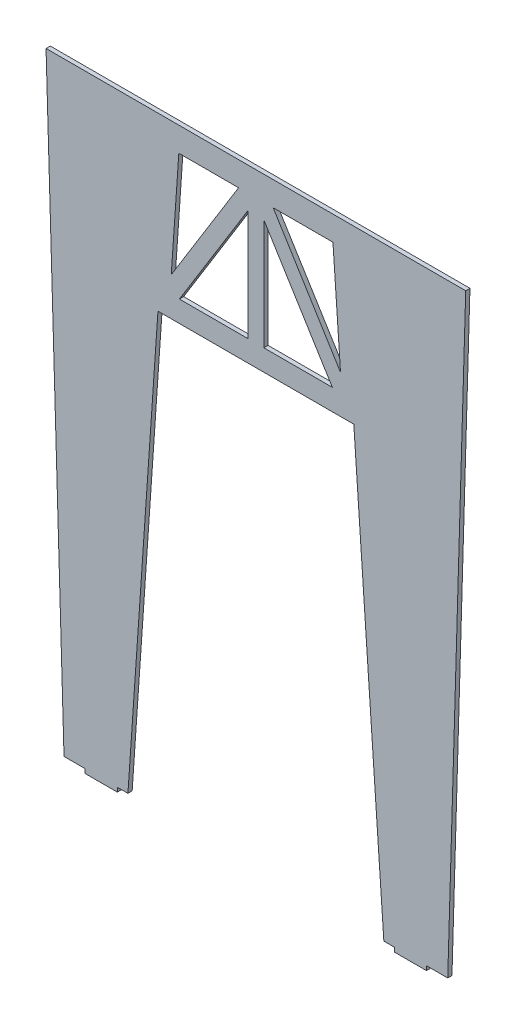
SolidWorks part; units mm, degrees
material "A-Glass Fiber"
ref_plane "Front Plane" through (0, 0, 0) normal (0, 0, 1) x (1, 0, 0)
ref_plane "Top Plane" through (0, 0, 0) normal (0, 1, 0) x (1, 0, 0)
ref_plane "Right Plane" through (0, 0, 0) normal (1, 0, 0) x (0, 0, -1)
sketch "Sketch1" plane through (0, 0, 0) normal (0, 0, 1) x (1, 0, 0)
  line L0 (-288.2759, 0) -> (288.2759, 0) construction
  line L1 (-215.8925, 1465.1633) -> (215.8925, 1465.1633)
  line L2 (0, 0) -> (0, 1733.4513) construction
  line L3 (19.05, 1104.9) -> (205.6376, 1104.9)
  line L4 (202.8026, 1145.716) -> (41.4459, 1406.7433)
  line L5 (205.6376, 1104.9) -> (19.05, 1406.7433) construction
  line L6 (205.6376, 1104.9) -> (184.6725, 1406.7433)
  line L7 (183.2417, 1104.9) -> (15.2162, 1376.7154)
  line L8 (19.05, 1406.7433) -> (19.05, 1104.9)
  line L9 (184.6725, 1406.7433) -> (19.05, 1406.7433)
  line L10 (306.6278, 17.4764) -> (234.6272, 1054.1)
  line L12 (459.7218, 17.4764) -> (502.7833, 1465.1633)
  line L13 (459.7218, 7.3164) -> (520.3601, 2060.2279) construction
  line L15 (266.6925, 1465.1633) -> (368.5375, 1465.1633)
  line L16 (-237.2124, 1016.8799) -> (-230.6925, 1110.7494) construction
  line L18 (237.2124, 1016.8799) -> (230.6925, 1110.7494) construction
  line L19 (-408.9218, 7.3164) -> (-332.1008, 7.3164)
  line L20 (-502.7833, 1465.1633) -> (-215.8925, 1465.1633)
  line L22 (408.9218, 7.3164) -> (332.7218, 7.3164)
  line L24 (-408.9218, 17.4764) -> (-408.9218, 7.3164) construction
  line L30 (-408.9218, 17.4764) -> (-408.9218, 7.3164)
  line L31 (502.7833, 1465.1633) -> (368.5375, 1465.1633)
  line L32 (-332.1008, 17.4764) -> (-332.1008, 7.3164) construction
  line L33 (-332.1008, 17.4764) -> (-332.1008, 7.3164)
  line L34 (408.9218, 17.4764) -> (408.9218, 7.3164) construction
  line L35 (408.9218, 17.4764) -> (408.9218, 7.3164)
  line L40 (332.7218, 17.4764) -> (332.7218, 7.3164) construction
  line L43 (332.7218, 17.4764) -> (332.7218, 7.3164)
  line L44 (459.7218, 17.4764) -> (408.9218, 17.4764) construction
  line L45 (459.7218, 17.4764) -> (408.9218, 17.4764)
  line L49 (-408.9218, 17.4764) -> (-459.7218, 17.4764)
  line L52 (-332.1008, 17.4764) -> (-306.6278, 17.4764)
  line L53 (332.7218, 17.4764) -> (306.6278, 17.4764)
  line L55 (-459.7218, 17.4764) -> (-502.7833, 1465.1633)
  line L56 (-459.7218, 7.3164) -> (-520.3601, 2060.2279) construction
  line L81 (215.8925, 1465.1633) -> (266.6925, 1465.1633)
  line L90 (234.6272, 1054.1) -> (-234.6272, 1054.1)
  line L100 (-234.6272, 1054.1) -> (-306.6278, 17.4764)
  line L124 (-184.6725, 1406.7433) -> (-19.05, 1406.7433)
  line L125 (-19.05, 1406.7433) -> (-19.05, 1104.9)
  line L126 (-183.2417, 1104.9) -> (-15.2162, 1376.7154)
  line L127 (-205.6376, 1104.9) -> (-19.05, 1406.7433) construction
  line L128 (-202.8026, 1145.716) -> (-41.4459, 1406.7433)
  line L129 (-205.6376, 1104.9) -> (-184.6725, 1406.7433)
  line L130 (-19.05, 1104.9) -> (-205.6376, 1104.9)
  point P0 (0, 0)
  point P1 (-316.1111, 17.4764)
  point P3 (0, 0)
  point P18 (450.2385, 17.4764)
  point P20 (307.2622, 17.4764)
  point P23 (0, 0)
  point P24 (-254.2769, 1054.1)
  point P36 (-244.1104, 1054.1)
  point P40 (-316.1111, 17.4764)
  point P41 (-326.2288, 18.1791)
  point P42 (0, 0)
  point P43 (225.1439, 1054.1)
  point P45 (299.3354, 17.4764)
  point P46 (0, 0)
  point P48 (0, 0)
  point P106 (0, 0)
  point P118 (0, 1054.1)
  dimension "D6" = 25.4
  dimension "D7" = 50.8
  dimension "D8" = 58.42
  dimension "D9" = 19.05
  dimension "D19" = 288.2759
  dimension "D22" = 19.05
  dimension "D23" = 19.05
  dimension "D24" = 1054.1
  dimension "D49" = 50.8
extrude "Boss-Extrude1" add sketch "Sketch1" along normal blind 10.16 contours L20 | L100 L90 L125 L130 L129 L124 | L100 | L130 L126 L125 L124 L128 L129 | L81 | L4 L9 L8 L7 L3 L6 | L15 region at (0, 1447.4532, 0) region at (111.9691, 1256.3298, 0) region at (-111.9691, 1256.3298, 0)
fillet "Fillet1" [suppressed] radius 19.05
sketch "Sketch2" plane through (0, 0, 0) normal (0, 0, 1) x (1, 0, 0)
  line L18 (-222.6942, 1372.2749) -> (-212.5765, 1371.5721) construction
  line L56 (-216.5353, 1460.9479) -> (-222.6942, 1372.2749) construction
  line L57 (-212.5765, 1371.5721) -> (-206.3688, 1460.9479) construction
  line L58 (-206.3688, 1460.9479) -> (-216.5353, 1460.9479) construction
  line L59 (-222.6942, 1372.2749) -> (-212.5765, 1371.5721)
  line L61 (-216.5353, 1460.9479) -> (-222.6942, 1372.2749)
  line L63 (-212.5765, 1371.5721) -> (-206.3688, 1460.9479)
  line L72 (254.6785, 758.0961) -> (261.1947, 664.2796) construction
  line L73 (261.1947, 664.2796) -> (271.3124, 664.9824) construction
  line L74 (271.3124, 664.9824) -> (264.7962, 758.7989) construction
  line L75 (264.7962, 758.7989) -> (254.6785, 758.0961) construction
  line L76 (266.9983, 580.7234) -> (273.5126, 486.9335) construction
  line L77 (273.5126, 486.9335) -> (283.6303, 487.6362) construction
  line L78 (283.6303, 487.6362) -> (277.1159, 581.4262) construction
  line L79 (277.1159, 581.4262) -> (266.9983, 580.7234) construction
  line L80 (279.318, 403.3508) -> (285.8305, 309.5874) construction
  line L81 (285.8305, 309.5874) -> (295.9482, 310.2901) construction
  line L82 (295.9482, 310.2901) -> (289.4357, 404.0535) construction
  line L83 (289.4357, 404.0535) -> (279.318, 403.3508) construction
  line L84 (291.6378, 225.9781) -> (298.1484, 132.2412) construction
  line L85 (298.1484, 132.2412) -> (308.2661, 132.944) construction
  line L86 (308.2661, 132.944) -> (301.7555, 226.6808) construction
  line L87 (301.7555, 226.6808) -> (291.6378, 225.9781) construction
  line L160 (254.6785, 758.0961) -> (261.1947, 664.2796)
  line L161 (261.1947, 664.2796) -> (271.3124, 664.9824)
  line L162 (271.3124, 664.9824) -> (264.7962, 758.7989)
  line L163 (264.7962, 758.7989) -> (254.6785, 758.0961)
  line L164 (266.9983, 580.7234) -> (273.5126, 486.9335)
  line L165 (273.5126, 486.9335) -> (283.6303, 487.6362)
  line L166 (283.6303, 487.6362) -> (277.1159, 581.4262)
  line L167 (277.1159, 581.4262) -> (266.9983, 580.7234)
  line L168 (279.318, 403.3508) -> (285.8305, 309.5874)
  line L169 (285.8305, 309.5874) -> (295.9482, 310.2901)
  line L170 (295.9482, 310.2901) -> (289.4357, 404.0535)
  line L171 (289.4357, 404.0535) -> (279.318, 403.3508)
  line L172 (291.6378, 225.9781) -> (298.1484, 132.2412)
  line L173 (298.1484, 132.2412) -> (308.2661, 132.944)
  line L174 (308.2661, 132.944) -> (301.7555, 226.6808)
  line L175 (301.7555, 226.6808) -> (291.6378, 225.9781)
  line L176 (-206.3688, 1460.9479) -> (-216.5353, 1460.9479)
  line L181 (-224.8945, 1194.226) -> (-235.0121, 1194.9287) construction
  line L194 (-224.8945, 1194.226) -> (-218.3727, 1288.1221) construction
  line L199 (-218.3727, 1288.1221) -> (-228.4904, 1288.8248) construction
  line L208 (-228.4904, 1288.8248) -> (-235.0121, 1194.9287) construction
  line L213 (-224.8945, 1194.226) -> (-235.0121, 1194.9287)
  line L270 (-261.1947, 664.2796) -> (-254.6785, 758.0961) construction
  line L271 (-254.6785, 758.0961) -> (-264.7962, 758.7989) construction
  line L272 (-264.7962, 758.7989) -> (-271.3124, 664.9824) construction
  line L273 (-271.3124, 664.9824) -> (-261.1947, 664.2796) construction
  line L274 (-273.5126, 486.9335) -> (-266.9983, 580.7234) construction
  line L275 (-266.9983, 580.7234) -> (-277.1159, 581.4262) construction
  line L276 (-277.1159, 581.4262) -> (-283.6303, 487.6362) construction
  line L277 (-283.6303, 487.6362) -> (-273.5126, 486.9335) construction
  line L278 (-285.8305, 309.5874) -> (-279.318, 403.3508) construction
  line L279 (-279.318, 403.3508) -> (-289.4357, 404.0535) construction
  line L280 (-289.4357, 404.0535) -> (-295.9482, 310.2901) construction
  line L281 (-295.9482, 310.2901) -> (-285.8305, 309.5874) construction
  line L282 (-298.1484, 132.2412) -> (-291.6378, 225.9781) construction
  line L283 (-291.6378, 225.9781) -> (-301.7555, 226.6808) construction
  line L284 (-301.7555, 226.6808) -> (-308.2661, 132.944) construction
  line L285 (-308.2661, 132.944) -> (-298.1484, 132.2412) construction
  line L314 (-261.1947, 664.2796) -> (-254.6785, 758.0961)
  line L315 (-254.6785, 758.0961) -> (-264.7962, 758.7989)
  line L316 (-264.7962, 758.7989) -> (-271.3124, 664.9824)
  line L317 (-271.3124, 664.9824) -> (-261.1947, 664.2796)
  line L318 (-273.5126, 486.9335) -> (-266.9983, 580.7234)
  line L319 (-266.9983, 580.7234) -> (-277.1159, 581.4262)
  line L320 (-277.1159, 581.4262) -> (-283.6303, 487.6362)
  line L321 (-283.6303, 487.6362) -> (-273.5126, 486.9335)
  line L322 (-285.8305, 309.5874) -> (-279.318, 403.3508)
  line L323 (-279.318, 403.3508) -> (-289.4357, 404.0535)
  line L324 (-289.4357, 404.0535) -> (-295.9482, 310.2901)
  line L325 (-295.9482, 310.2901) -> (-285.8305, 309.5874)
  line L326 (-298.1484, 132.2412) -> (-291.6378, 225.9781)
  line L327 (-291.6378, 225.9781) -> (-301.7555, 226.6808)
  line L328 (-301.7555, 226.6808) -> (-308.2661, 132.944)
  line L329 (-308.2661, 132.944) -> (-298.1484, 132.2412)
  line L330 (-224.8945, 1194.226) -> (-218.3727, 1288.1221)
  line L331 (-218.3727, 1288.1221) -> (-228.4904, 1288.8248)
  line L332 (-228.4904, 1288.8248) -> (-235.0121, 1194.9287)
  line L333 (224.8945, 1194.226) -> (235.0121, 1194.9287) construction
  line L334 (235.0121, 1194.9287) -> (228.4904, 1288.8248) construction
  line L335 (218.3727, 1288.1221) -> (224.8945, 1194.226) construction
  line L336 (228.4904, 1288.8248) -> (218.3727, 1288.1221) construction
  line L337 (212.5765, 1371.5721) -> (222.6942, 1372.2749) construction
  line L338 (206.3688, 1460.9479) -> (212.5765, 1371.5721) construction
  line L339 (216.5353, 1460.9479) -> (206.3688, 1460.9479) construction
  line L340 (222.6942, 1372.2749) -> (216.5353, 1460.9479) construction
  line L341 (224.8945, 1194.226) -> (235.0121, 1194.9287)
  line L342 (235.0121, 1194.9287) -> (228.4904, 1288.8248)
  line L343 (218.3727, 1288.1221) -> (224.8945, 1194.226)
  line L344 (228.4904, 1288.8248) -> (218.3727, 1288.1221)
  line L345 (212.5765, 1371.5721) -> (222.6942, 1372.2749)
  line L346 (206.3688, 1460.9479) -> (212.5765, 1371.5721)
  line L347 (216.5353, 1460.9479) -> (206.3688, 1460.9479)
  line L348 (222.6942, 1372.2749) -> (216.5353, 1460.9479)
  line L349 (-240.8102, 1111.4521) -> (-247.33, 1017.5826) construction
  line L350 (-247.33, 1017.5826) -> (-237.2124, 1016.8799) construction
  line L351 (-230.6925, 1110.7494) -> (-240.8102, 1111.4521) construction
  line L352 (-237.2124, 1016.8799) -> (-230.6925, 1110.7494) construction
  line L353 (-240.8102, 1111.4521) -> (-247.33, 1017.5826)
  line L354 (-247.33, 1017.5826) -> (-237.2124, 1016.8799)
  line L355 (-230.6925, 1110.7494) -> (-240.8102, 1111.4521)
  line L356 (-237.2124, 1016.8799) -> (-230.6925, 1110.7494)
  line L357 (237.2124, 1016.8799) -> (247.33, 1017.5826) construction
  line L358 (247.33, 1017.5826) -> (240.8102, 1111.4521) construction
  line L359 (230.6925, 1110.7494) -> (237.2124, 1016.8799) construction
  line L360 (240.8102, 1111.4521) -> (230.6925, 1110.7494) construction
  line L361 (237.2124, 1016.8799) -> (247.33, 1017.5826)
  line L362 (247.33, 1017.5826) -> (240.8102, 1111.4521)
  line L363 (230.6925, 1110.7494) -> (237.2124, 1016.8799)
  line L364 (240.8102, 1111.4521) -> (230.6925, 1110.7494)
  line L365 (-306.6278, 17.4764) -> (-234.6272, 1054.1)
  line L366 (-234.6272, 1054.1) -> (234.6272, 1054.1)
  line L367 (234.6272, 1054.1) -> (306.6278, 17.4764)
  line L368 (306.6278, 17.4764) -> (332.7218, 17.4764)
  line L369 (332.7218, 17.4764) -> (332.7218, 7.3164)
  line L370 (332.7218, 7.3164) -> (408.9218, 7.3164)
  line L371 (408.9218, 7.3164) -> (408.9218, 17.4764)
  line L372 (408.9218, 17.4764) -> (459.7218, 17.4764)
  line L373 (459.7218, 17.4764) -> (502.7833, 1465.1633)
  line L374 (502.7833, 1465.1633) -> (-502.7833, 1465.1633)
  line L375 (-502.7833, 1465.1633) -> (-459.7218, 17.4764)
  line L376 (-459.7218, 17.4764) -> (-408.9218, 17.4764)
  line L377 (-408.9218, 17.4764) -> (-408.9218, 7.3164)
  line L378 (-408.9218, 7.3164) -> (-332.1008, 7.3164)
  line L379 (-332.1008, 7.3164) -> (-332.1008, 17.4764)
  line L380 (-332.1008, 17.4764) -> (-306.6278, 17.4764)
  line L381 (-306.6278, 17.4764) -> (-234.6272, 1054.1)
  line L382 (-234.6272, 1054.1) -> (234.6272, 1054.1)
  line L383 (234.6272, 1054.1) -> (306.6278, 17.4764)
  line L384 (306.6278, 17.4764) -> (332.7218, 17.4764)
  line L385 (332.7218, 17.4764) -> (332.7218, 7.3164)
  line L386 (332.7218, 7.3164) -> (408.9218, 7.3164)
  line L387 (408.9218, 7.3164) -> (408.9218, 17.4764)
  line L388 (408.9218, 17.4764) -> (459.7218, 17.4764)
  line L389 (459.7218, 17.4764) -> (502.7833, 1465.1633)
  line L390 (502.7833, 1465.1633) -> (-502.7833, 1465.1633)
  line L391 (-502.7833, 1465.1633) -> (-459.7218, 17.4764)
  line L392 (-459.7218, 17.4764) -> (-408.9218, 17.4764)
  line L393 (-408.9218, 17.4764) -> (-408.9218, 7.3164)
  line L394 (-408.9218, 7.3164) -> (-332.1008, 7.3164)
  line L395 (-332.1008, 7.3164) -> (-332.1008, 17.4764)
  line L396 (-332.1008, 17.4764) -> (-306.6278, 17.4764)
  dimension "D1" = 0
extrude "Cut-Extrude1" cut sketch "Sketch2" against normal blind 12.7 contours L162 L163 L160 L161 | L166 L167 L164 L165 | L170 L171 L168 L169 | L174 L175 L172 L173 | L328 L329 L326 L327 | L324 L325 L322 L323 | L320 L321 L318 L319 | L316 L317 L314 L315 rebuild error yes
